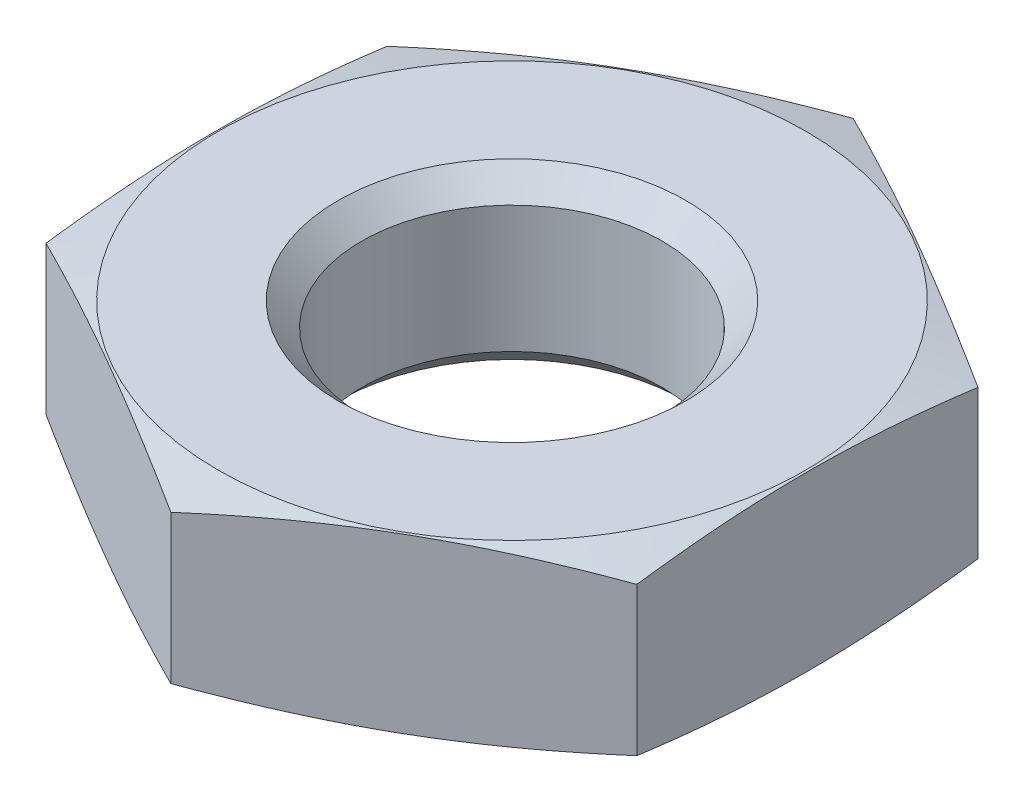
SolidWorks part; units mm, degrees
ref_plane "Front Plane" through (0, 0, 0) normal (0, 0, 1) x (1, 0, 0)
ref_plane "Top Plane" through (0, 0, 0) normal (0, 1, 0) x (1, 0, 0)
ref_plane "Right Plane" through (0, 0, 0) normal (1, 0, 0) x (0, 0, -1)
ref_plane "Plane1" through (0, 0, 0) normal (0, 0, 1) x (1, 0, 0)
sketch "Sketch1" plane through (0, 0, 0) normal (0, 0, 1) x (1, 0, 0)
  line L0 (0, 0) -> (8.45, 0)
  line L1 (8.45, 0) -> (17.7801, -2.5)
  line L2 (17.7801, -2.5) -> (8.45, -5)
  line L3 (8.45, -5) -> (0, -5)
  line L4 (0, -5) -> (0, 0)
  line L5 (0, -5) -> (0, 0) construction
revolve "Revolve1" add sketch "Sketch1" angle 360 about L5
ref_plane "Plane2" through (0, 0, 0) normal (0, 1, 0) x (1, 0, 0)
sketch "Sketch2" plane through (0, 0, 0) normal (0, 1, 0) x (1, 0, 0)
  line L0 (-34, 34) -> (-34, -34)
  line L1 (-34, -34) -> (34, -34)
  line L2 (34, -34) -> (34, 34)
  line L3 (34, 34) -> (-34, 34)
  line L4 (-8.5, -4.9075) -> (0, -9.815)
  line L5 (0, -9.815) -> (8.5, -4.9075)
  line L6 (8.5, -4.9075) -> (8.5, 4.9075)
  line L7 (8.5, 4.9075) -> (0, 9.815)
  line L8 (0, 9.815) -> (-8.5, 4.9075)
  line L9 (-8.5, 4.9075) -> (-8.5, -4.9075)
extrude "Cut-Extrude1" cut sketch "Sketch2" against normal blind 6 and the other way blind 6
ref_plane "Plane3" through (0, 0, 0) normal (0, 0, 1) x (1, 0, 0)
sketch "Sketch3" plane through (0, 0, 0) normal (0, 0, 1) x (1, 0, 0)
  line L0 (0, 0) -> (5, 0)
  line L1 (5, 0) -> (4.3235, -0.6765)
  line L2 (4.3235, -0.6765) -> (4.3235, -4.3235)
  line L3 (4.3235, -4.3235) -> (5, -5)
  line L4 (5, -5) -> (0, -5)
  line L5 (0, -5) -> (0, 0)
  line L6 (0, -5) -> (0, 0) construction
revolve "Cut-Revolve1" cut sketch "Sketch3" angle 360 about L6 reverse direction yes
cosmetic thread "Cosmetic Thread1" parameters "D1"=5, "D2"=10
